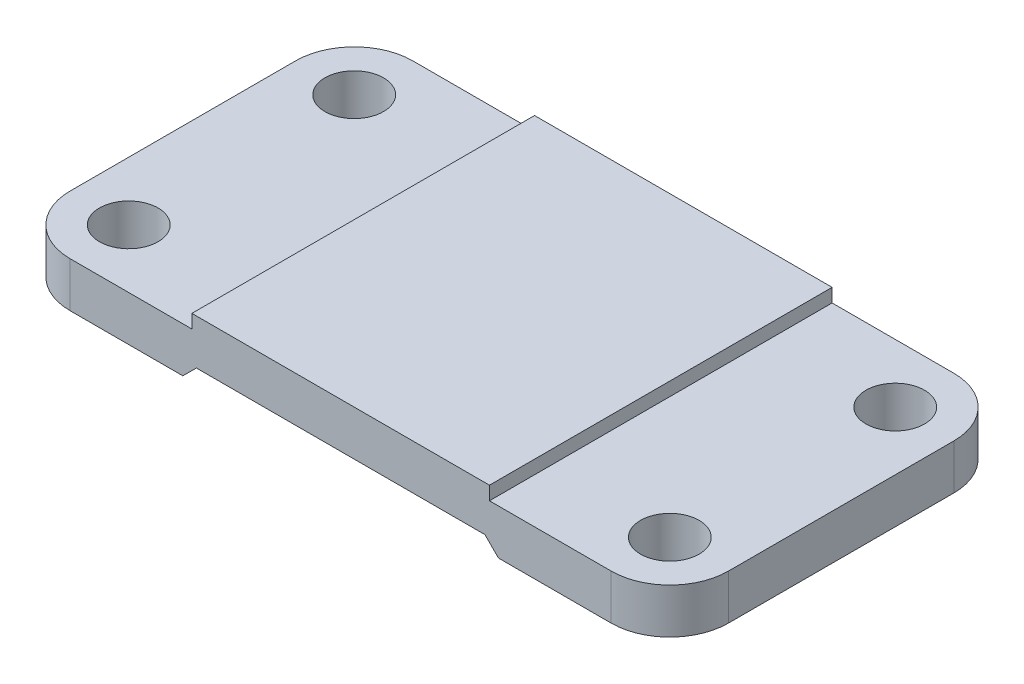
SolidWorks part; units mm, degrees
ref_plane "Alzado" through (0, 0, 0) normal (0, 0, 1) x (1, 0, 0)
ref_plane "Planta" through (0, 0, 0) normal (0, 1, 0) x (1, 0, 0)
ref_plane "Vista lateral" through (0, 0, 0) normal (1, 0, 0) x (0, 0, -1)
sketch "Croquis2" plane through (0, 0, 0) normal (0, 1, 0) x (1, 0, 0)
  line L1 (-73, -38) -> (73, -38)
  line L2 (-73, -38) -> (-73, 38)
  line L3 (-73, 38) -> (73, 38)
  line L4 (73, -38) -> (73, 38)
  line L5 (-73, -38) -> (73, 38) construction
  line L6 (-73, 38) -> (73, -38) construction
  point P0 (0, 0)
  dimension "D1" = 146
  dimension "D2" = 76
extrude "Saliente-Extruir2" add sketch "Croquis2" along normal blind 10
sketch "Croquis3" plane through (0, 10, 0) normal (0, 1, 0) x (1, 0, 0)
  line L0 (0, 0) -> (33, 0) construction
  line L1 (33, 38) -> (33, -38)
  line L2 (73, 38) -> (-73, 38) construction
  line L3 (-73, -38) -> (73, -38) construction
  line L4 (0, 0) -> (-33, 0) construction
  line L5 (-33, 38) -> (-33, -38)
  line L6 (-33, 38) -> (33, 38)
  line L7 (-33, -38) -> (33, -38)
  dimension "D1" = 33
  dimension "D2" = 33
extrude "Saliente-Extruir3" add sketch "Croquis3" along normal blind 3
fillet "Redondeo1" radius 13 1 edges at (-73, 5, -38) type face fillet first side face at (0, 8.25, -38) second side face at (-73, 5, 0)
fillet "Redondeo2" radius 13 1 edges at (-73, 5, 38) type face fillet first side face at (-73, 5, 6.5) second side face at (0, 8.25, 38)
fillet "Redondeo3" radius 13 1 edges at (73, 5, 38) type face fillet first side face at (3.25, 8.25, 38) second side face at (73, 5, 0)
fillet "Redondeo4" radius 13 1 edges at (73, 5, -38) type face fillet first side face at (3.25, 8.25, -38) second side face at (73, 5, -6.5)
sketch "Croquis5" plane through (0, 10, 0) normal (0, 1, 0) x (1, 0, 0)
  circle A0 centre (-60, 25) radius 6.5
  circle A1 centre (-60, -25) radius 6.5
  circle A2 centre (60, -25) radius 6.5
  circle A3 centre (60, 25) radius 6.5
  dimension "D1" = 13
  dimension "D2" = 13
  dimension "D3" = 13
  dimension "D4" = 13
extrude "Cortar-Extruir1" cut sketch "Croquis5" against normal through all
sketch "Croquis6" plane through (0, 0, 0) normal (0, -1, 0) x (1, 0, 0)
  line L0 (0, 0) -> (-36, 0) construction
  line L1 (-36, 38) -> (-36, -38)
  line L2 (-60, 38) -> (60, 38) construction
  line L3 (60, -38) -> (-60, -38) construction
  line L4 (0, 0) -> (36, 0) construction
  line L5 (36, 38) -> (36, -38)
  line L6 (-36, 38) -> (36, 38)
  line L7 (-36, -38) -> (36, -38)
  dimension "D1" = 36
  dimension "D2" = 36
extrude "Cortar-Extruir2" cut sketch "Croquis6" against normal blind 3
chamfer "Chaflán1" distance 4 angle 45 1 edges at (-36, 3, 0)
chamfer "Chaflán2" distance 4 angle 45 1 edges at (36, 3, 0)
